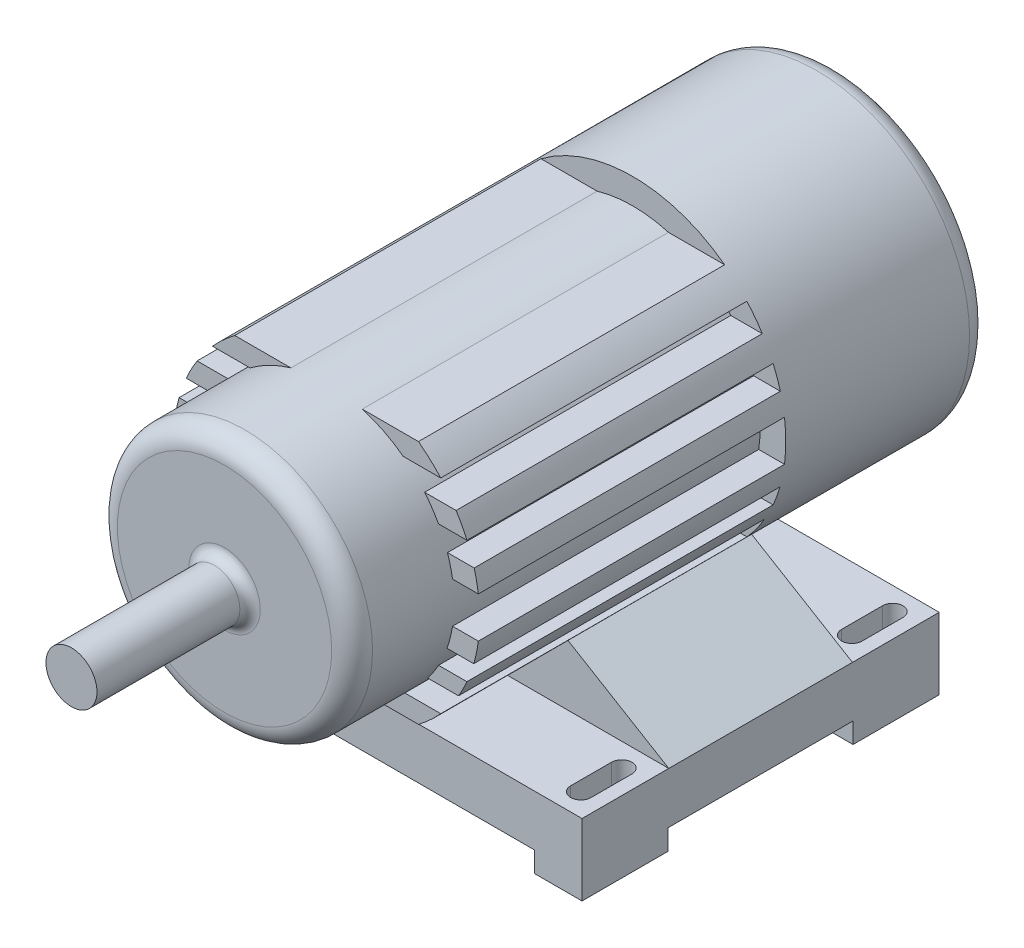
SolidWorks part; units mm, degrees
ref_plane "Front Plane" through (0, 0, 0) normal (0, 0, 1) x (1, 0, 0)
ref_plane "Top Plane" through (0, 0, 0) normal (0, 1, 0) x (1, 0, 0)
ref_plane "Right Plane" through (0, 0, 0) normal (1, 0, 0) x (0, 0, -1)
sketch "Sketch1" plane through (0, 0, 0) normal (0, 0, 1) x (1, 0, 0)
  circle A0 centre (0, 0) radius 150
  dimension "D1" = 300
extrude "Boss-Extrude1" add sketch "Sketch1" along normal blind 200
sketch "Sketch7" plane through (0, 0, 200) normal (0, 0, 1) x (1, 0, 0)
  line L0 (0, 0) -> (0, 100) construction
  line L1 (-90, 120) -> (90, 120)
  line L3 (-111.8034, 100) -> (111.8034, 100)
  line L4 (-126.8858, 80) -> (126.8858, 80)
  line L5 (-137.4773, 60) -> (137.4773, 60)
  line L6 (144.1634, -41.4356) -> (-144.1634, -41.4356)
  line L7 (111.8034, -100) -> (-111.8034, -100)
  line L8 (148.6607, -20) -> (-148.6607, -20)
  line L9 (90, -120) -> (-90, -120)
  line L10 (144.5683, 40) -> (-144.5683, 40)
  line L11 (148.6607, 20) -> (-148.6607, 20)
  line L12 (137.4773, -60) -> (-137.4773, -60)
  line L13 (129.2326, -76.1507) -> (-129.2326, -76.1507)
  arc A0 (-90, 120) -> (-111.8034, 100) centre (0, 0) ccw
  circle A1 centre (0, 0) radius 150 construction
  arc A2 (111.8034, 100) -> (90, 120) centre (0, 0) ccw
  arc A3 (-126.8858, 80) -> (-137.4773, 60) centre (0, 0) ccw
  arc A4 (137.4773, 60) -> (126.8858, 80) centre (0, 0) ccw
  arc A5 (-144.5683, 40) -> (-148.6607, 20) centre (0, 0) ccw
  arc A6 (148.6607, 20) -> (144.5683, 40) centre (0, 0) ccw
  arc A7 (-148.6607, -20) -> (-144.1634, -41.4356) centre (0, 0) ccw
  arc A8 (90, -120) -> (111.8034, -100) centre (0, 0) ccw
  arc A9 (129.2326, -76.1507) -> (137.4773, -60) centre (0, 0) ccw
  arc A10 (-111.8034, -100) -> (-90, -120) centre (0, 0) ccw
  arc A11 (-137.4773, -60) -> (-129.2326, -76.1507) centre (0, 0) ccw
  arc A12 (144.1634, -41.4356) -> (148.6607, -20) centre (0, 0) ccw
  dimension "D1" = 20
  dimension "D2" = 100
  dimension "D3" = 20
  dimension "D4" = 20
  dimension "D5" = 21.4356
  dimension "D6" = 20
  dimension "D7" = 16.1507
  dimension "D8" = 100
  dimension "D9" = 60
  dimension "D10" = 20
  dimension "D11" = 60
  dimension "D12" = 20
extrude "Boss-Extrude11" add sketch "Sketch7" along normal blind 300
sketch "Sketch12" plane through (0, 0, 500) normal (0, 0, 1) x (1, 0, 0)
  circle A0 centre (0, 0) radius 125
  dimension "D1" = 250
extrude "Boss-Extrude14" add sketch "Sketch12" along normal blind 400 from surface separate body starting at face at (0, 0, 200)
ref_plane "Plane4" through (0, -220, 0) normal (0, -1, 0) x (-1, 0, 0)
sketch "Sketch13" plane through (0, -220, 0) normal (0, -1, 0) x (-1, 0, 0)
  line L0 (0, -449.7357) -> (0, 0) construction
  line L1 (-200, -99.7357) -> (200, -99.7357)
  line L2 (-200, -99.7357) -> (-200, -449.7357)
  line L3 (-200, -449.7357) -> (200, -449.7357)
  line L4 (200, -99.7357) -> (200, -449.7357)
  line L5 (150, 0) -> (-150, 0) construction
  line L6 (200, -274.7357) -> (-200, -274.7357) construction
  line L7 (200, -184.1891) -> (150, -184.1891)
  line L8 (-153.3221, -99.7357) -> (-153.3221, -184.1891)
  line L9 (-153.3221, -184.1891) -> (-200, -184.1891)
  line L10 (150, -184.1891) -> (150, -99.7357)
  line L11 (175, -121.9624) -> (175, -161.9624) construction
  line L12 (185, -121.9624) -> (185, -161.9624)
  line L13 (165, -121.9624) -> (165, -161.9624)
  line L14 (-176.661, -121.9624) -> (-176.661, -161.9624) construction
  line L15 (-166.661, -121.9624) -> (-166.661, -161.9624)
  line L16 (-186.661, -121.9624) -> (-186.661, -161.9624)
  line L17 (-176.661, -427.509) -> (-176.661, -387.509) construction
  line L18 (-166.661, -427.509) -> (-166.661, -387.509)
  line L19 (-186.661, -427.509) -> (-186.661, -387.509)
  line L20 (-153.3221, -365.2823) -> (-200, -365.2823)
  line L21 (-153.3221, -449.7357) -> (-153.3221, -365.2823)
  line L22 (175, -427.509) -> (175, -387.509) construction
  line L23 (185, -427.509) -> (185, -387.509)
  line L24 (165, -427.509) -> (165, -387.509)
  line L25 (200, -365.2823) -> (150, -365.2823)
  line L26 (150, -365.2823) -> (150, -449.7357)
  arc A0 (185, -121.9624) -> (165, -121.9624) centre (175, -121.9624) ccw
  arc A1 (165, -161.9624) -> (185, -161.9624) centre (175, -161.9624) ccw
  arc A2 (-166.661, -121.9624) -> (-186.661, -121.9624) centre (-176.661, -121.9624) ccw
  arc A3 (-186.661, -161.9624) -> (-166.661, -161.9624) centre (-176.661, -161.9624) ccw
  arc A4 (-166.661, -427.509) -> (-186.661, -427.509) centre (-176.661, -427.509) cw
  arc A5 (-186.661, -387.509) -> (-166.661, -387.509) centre (-176.661, -387.509) cw
  arc A6 (185, -427.509) -> (165, -427.509) centre (175, -427.509) cw
  arc A7 (165, -387.509) -> (185, -387.509) centre (175, -387.509) cw
  point P19 (175, -141.9624)
  point P24 (150, -141.9624)
  point P26 (175, -184.1891)
  point P28 (-176.661, -141.9624)
  point P33 (-176.661, -184.1891)
  point P34 (-153.3221, -141.9624)
  point P37 (-176.661, -407.509)
  point P47 (175, -407.509)
  dimension "D7" = 10
  dimension "D9" = 10
  dimension "D1" = 99.7357
  dimension "D2" = 350
  dimension "D3" = 400
  dimension "D4" = 84.4534
  dimension "D5" = 46.6779
  dimension "D6" = 50
  dimension "D8" = 40
  dimension "D10" = 40
extrude "Boss-Extrude15" add sketch "Sketch13" against normal blind 50 separate body contours L26 L25 L4 L7 L10 L1 L8 L9 L2 L20 L21 L3 | L9 L8 L1 L2 A3 L16 A2 L15 | L3 L21 L20 L2 L19 A5 L18 A4 | L25 L26 L3 L4 L24 A7 L23 A6 | L10 L7 L4 L1 A1 L13 A0 L12 region at (176.661, -220, 100.7007) region at (0.6881, -220, 274.7357) region at (-175, -220, 100.7172) region at (176.661, -220, 366.2473) region at (-199.0186, -220, 407.509)
extrude "Boss-Extrude16" add sketch "Sketch13<3>" along normal blind 20 contours L3 L21 L20 L2 L19 A5 L18 A4 | L9 L8 L1 L2 A3 L16 A2 L15 | L25 L26 L3 L4 L24 A7 L23 A6 | L10 L7 L4 L1 A1 L13 A0 L12 region at (176.661, -220, 100.7007) region at (-175, -220, 100.7172) region at (176.661, -220, 366.2473) region at (-199.0186, -220, 407.509)
sketch "Sketch13<3>" plane through (0, -220, 0) normal (0, -1, 0) x (-1, 0, 0) same geometry as "Sketch13"
ref_plane "Plane5" through (0, 0, 274.7357) normal (0, 0, 1) x (1, 0, 0)
sketch "Sketch14" plane through (0, 0, 274.7357) normal (0, 0, 1) x (1, 0, 0)
  line L0 (-200, -170) -> (200, -170)
  line L1 (200, -170) -> (100, -110)
  line L2 (100, -110) -> (-100, -110)
  line L3 (-100, -110) -> (-200, -170)
  line L4 (200, -170) -> (-200, -170) construction
  dimension "D1" = 60
  dimension "D2" = 200
extrude "Boss-Extrude17" add sketch "Sketch14" along normal mid plane 180
sketch "Sketch16" plane through (0, 0, 600) normal (0, 0, 1) x (1, 0, 0)
  circle A0 centre (0, 0) radius 25
  dimension "D1" = 50
extrude "Boss-Extrude18" add sketch "Sketch16" along normal blind 150
fillet "Fillet2" radius 10 1 edges at (25, 0, 600)
fillet "Fillet3" radius 20 2 edges at (150, 0, 0) (125, 0, 600)
